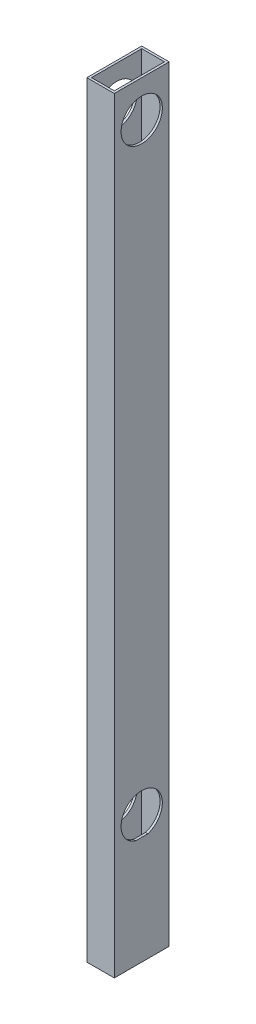
SolidWorks part; units mm, degrees
ref_plane "Front Plane" through (0, 0, 0) normal (0, 0, 1) x (1, 0, 0)
ref_plane "Top Plane" through (0, 0, 0) normal (0, 1, 0) x (1, 0, 0)
ref_plane "Right Plane" through (0, 0, 0) normal (1, 0, 0) x (0, 0, -1)
sketch "Sketch1" plane through (0, 0, 0) normal (0, 1, 0) x (1, 0, 0)
  line L1 (0, 0) -> (19.05, 0)
  line L2 (0, 0) -> (0, 38.1)
  line L3 (0, 38.1) -> (19.05, 38.1)
  line L4 (19.05, 0) -> (19.05, 38.1)
  dimension "D1" = 38.1
  dimension "D2" = 19.05
extrude "Extrude-Thin1" add sketch "Sketch1" along normal blind 457.2 thin thin type one direction reverse wall 1.5875
sketch "Sketch2" plane through (19.05, 0, 0) normal (1, 0, 0) x (0, 0, -1)
  line L0 (0, 0) -> (38.1, 0) construction
  line L1 (0, 457.2) -> (0, 0) construction
  line L2 (0, 457.2) -> (38.1, 457.2) construction
  circle A0 centre (19.05, 13.716) radius 14.351
  circle A1 centre (19.05, 431.8) radius 14.351
  dimension "D1" = 13.716
  dimension "D2" = 28.702
  dimension "D4" = 25.4
  dimension "D5" = 28.702
  dimension "D6" = 19.05
  dimension "D3" = 19.05
extrude "Cut-Extrude1" cut sketch "Sketch2" against normal through all both and the other way through all
sketch "Sketch3" plane through (0, 0, 0) normal (0, -1, 0) x (-1, 0, 0)
  line L1 (-19.05, 38.1) -> (0, 38.1)
  line L2 (-19.05, 38.1) -> (-19.05, 0)
  line L3 (-19.05, 0) -> (0, 0)
  line L4 (0, 38.1) -> (0, 0)
extrude "Extrude-Thin2" add sketch "Sketch3" along normal blind 75.184 thin thin type one direction reverse wall 1.5875
